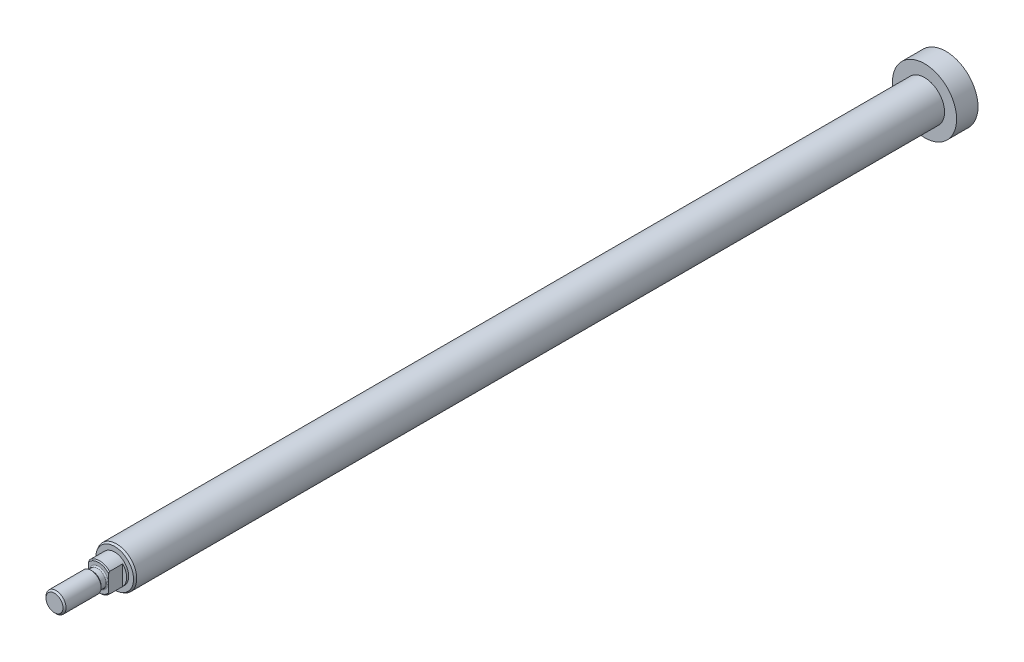
SolidWorks part; units mm, degrees
ref_plane "Front Plane" through (0, 0, 0) normal (0, 0, 1) x (1, 0, 0)
ref_plane "Top Plane" through (0, 0, 0) normal (0, 1, 0) x (1, 0, 0)
ref_plane "Right Plane" through (0, 0, 0) normal (1, 0, 0) x (0, 0, -1)
sketch "Sketch1" plane through (0, 0, 0) normal (1, 0, 0) x (0, 0, -1)
  line L0 (-25.5, 0) -> (-25.5, 6.5)
  line L1 (-25.5, 6.5) -> (-25, 7)
  line L2 (-25, 7) -> (-17.5, 7)
  line L3 (-17.5, 7) -> (-17.5, 9.4226)
  line L4 (-17.5, 9.4226) -> (-16.5, 10)
  line L5 (-16.5, 10) -> (386.3333, 10)
  line L6 (386.3333, 10) -> (386.3333, 16)
  line L7 (386.3333, 16) -> (397, 16)
  line L8 (397, 16) -> (397, 0)
  line L9 (397, 0) -> (-25.5, 0)
  line L10 (397, 0) -> (-25.5, 0) construction
revolve "Revolve1" add sketch "Sketch1" angle 360 about L10 reverse direction yes
sketch "Sketch2" plane through (0, 0, 0) normal (0, 1, 0) x (1, 0, 0)
  line L0 (-8, -18.5) -> (-8, -28.5)
  line L1 (-8, -28.5) -> (8, -28.5)
  line L2 (8, -28.5) -> (8, -18.5)
  line L3 (8, -18.5) -> (5, -18.5)
  line L4 (5, -18.5) -> (5, -25.5)
  line L5 (5, -25.5) -> (-5, -25.5)
  line L6 (-5, -25.5) -> (-5, -18.5)
  line L7 (-5, -18.5) -> (-8, -18.5)
extrude "Cut-Extrude1" cut sketch "Sketch2" along normal blind 14 and the other way blind 14
sketch "Sketch3" plane through (0, 0, 0) normal (1, 0, 0) x (0, 0, -1)
  line L0 (-47.5, 0) -> (-47.5, 4.233)
  line L1 (-47.5, 4.233) -> (-46.733, 5)
  line L2 (-46.733, 5) -> (-29.267, 5)
  line L3 (-29.267, 5) -> (-28.5, 4.233)
  line L4 (-28.5, 4.233) -> (-26.1, 4.233)
  line L5 (-25.5, 4.833) -> (-25.5, 0)
  line L6 (-25.5, 0) -> (-47.5, 0)
  line L7 (-25.5, 0) -> (-47.5, 0) construction
  arc A0 (-26.1, 4.233) -> (-25.5, 4.833) centre (-26.1, 4.833) ccw
revolve "Revolve2" add sketch "Sketch3" angle 360 about L7 reverse direction yes
cosmetic thread "Cosmetic Thread1" parameters "D1"=19, "D2"=8.466
ref_plane "Plane4" through (0, 0, -397) normal (0, 0, 1) x (1, 0, 0)
ref_plane "Plane5" through (0, 0, 33) normal (0, 0, 1) x (1, 0, 0)
ref_plane "ANBAU XY" through (0, 0, -397) normal (0, 0, -1) x (-1, 0, 0)
ref_plane "ANBAU XZ" through (0, 0, 0) normal (0, 1, 0) x (1, 0, 0)
ref_plane "ANBAU YZ" through (0, 0, 0) normal (1, 0, 0) x (0, 0, -1)
ref_axis "ANBAU X" through (-80.9, 0, -397) along (1, 0, 0)
ref_axis "ANBAU Y" through (0, 50, -397) along (0, -1, 0)
ref_axis "ANBAU Z" through (0, 0, -80.9) along (0, 0, 1)
sketch3d "ANBAU"
  point P0 (0, 0, -397)
ref_plane "NUT XY" through (0, 0, 33) normal (0, 0, -1) x (-1, 0, 0)
ref_plane "NUT XZ" through (0, 0, 0) normal (0, 1, 0) x (1, 0, 0)
ref_plane "NUT YZ" through (0, 0, 0) normal (1, 0, 0) x (0, 0, -1)
ref_axis "NUT X" through (-80.9, 0, 33) along (1, 0, 0)
ref_axis "NUT Y" through (0, 50, 33) along (0, -1, 0)
ref_axis "NUT Z" through (0, 0, -80.9) along (0, 0, 1)
sketch3d "NUT"
  point P0 (0, 0, 33)
other "Freeze***"
